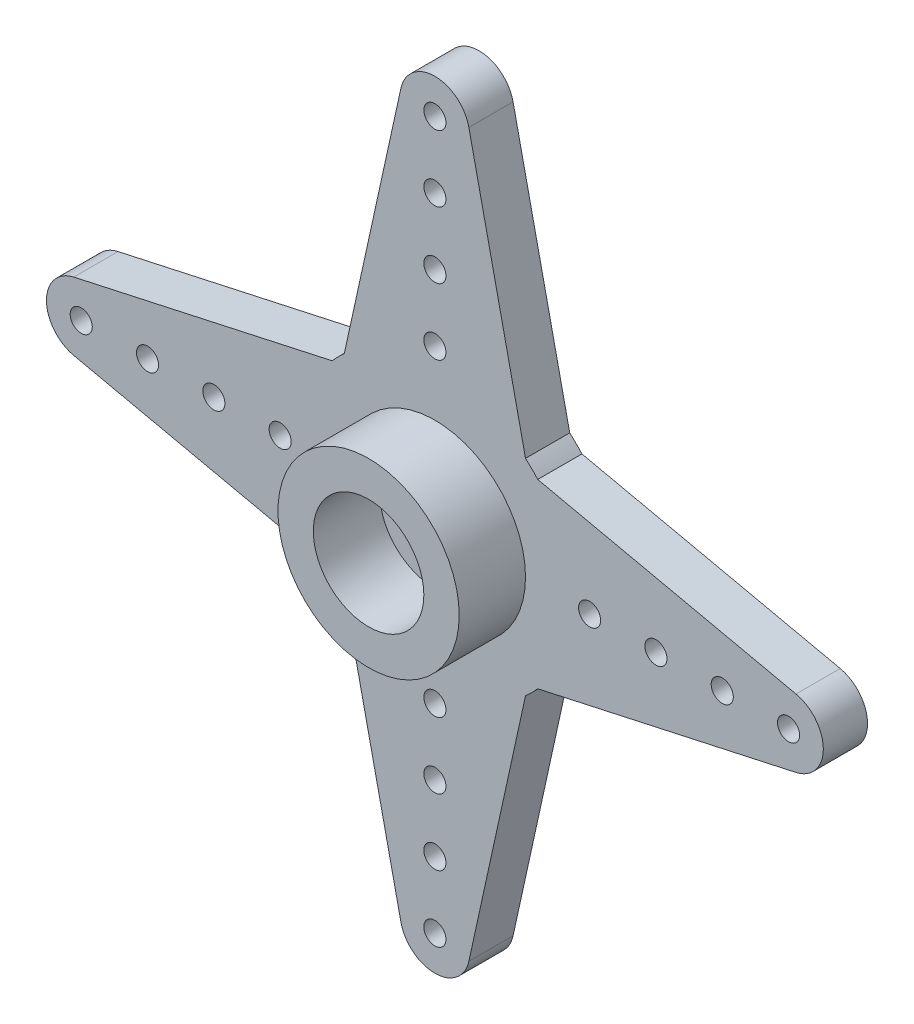
SolidWorks part; units mm, degrees
ref_plane "Front Plane" through (0, 0, 0) normal (0, 0, 1) x (1, 0, 0)
ref_plane "Top Plane" through (0, 0, 0) normal (0, 1, 0) x (1, 0, 0)
ref_plane "Right Plane" through (0, 0, 0) normal (1, 0, 0) x (0, 0, -1)
ref_axis "Axe1" through (0, 0, -0.25) along (0, 0, 1)
sketch "Esquisse1" plane through (0, 0, 0) normal (0, 0, 1) x (1, 0, 0)
  line L0 (-16.337, 1.5365) -> (-4.6508, 4.1)
  line L1 (4.6508, 4.1) -> (16.337, 1.5365)
  line L2 (16.337, -1.5365) -> (4.6508, -4.1)
  line L3 (-4.6508, -4.1) -> (-16.337, -1.5365)
  arc A0 (4.6508, 4.1) -> (-4.6508, 4.1) centre (0, 0) ccw
  arc A1 (16.337, -1.5365) -> (16.337, 1.5365) centre (16, 0) ccw
  arc A2 (4.6508, -4.1) -> (-4.6508, -4.1) centre (0, 0) cw
  arc A3 (-16.337, 1.5365) -> (-16.337, -1.5365) centre (-16, 0) ccw
  circle A4 centre (0, 0) radius 1.5
  circle A5 centre (7, 0) radius 0.5
  circle A6 centre (16, 0) radius 0.5
  circle A7 centre (13, 0) radius 0.5
  circle A8 centre (10, 0) radius 0.5
  circle A9 centre (-16, 0) radius 0.5
  circle A10 centre (-13, 0) radius 0.5
  circle A11 centre (-10, 0) radius 0.5
  circle A12 centre (-7, 0) radius 0.5
  dimension "D2" = 6.2
  dimension "D4" = 1.573
  dimension "D5" = 3
  dimension "D6" = 1
  dimension "D1" = 32
  dimension "D3" = 8.2
  dimension "D7" = 7
  dimension "D8" = 3
  dimension "D9" = 3
  dimension "D10" = 7
  dimension "D11" = 10
  dimension "D12" = 3
extrude "Boss.-Extru.1" add sketch "Esquisse1" along normal blind 2
sketch "Esquisse2" plane through (0, 0, 2) normal (0, 0, 1) x (1, 0, 0)
  circle A0 centre (0, 0) radius 4.1
  circle A1 centre (0, 0) radius 2.5
  dimension "D1" = 8.2
  dimension "D2" = 5
extrude "Boss.-Extru.2" add sketch "Esquisse2" along normal blind 3
pattern_circular "Répétition circulaire1" count 2 every 90 about axis through (0, 0, -0.25) along (0, 0, 1) of "Boss.-Extru.1"
